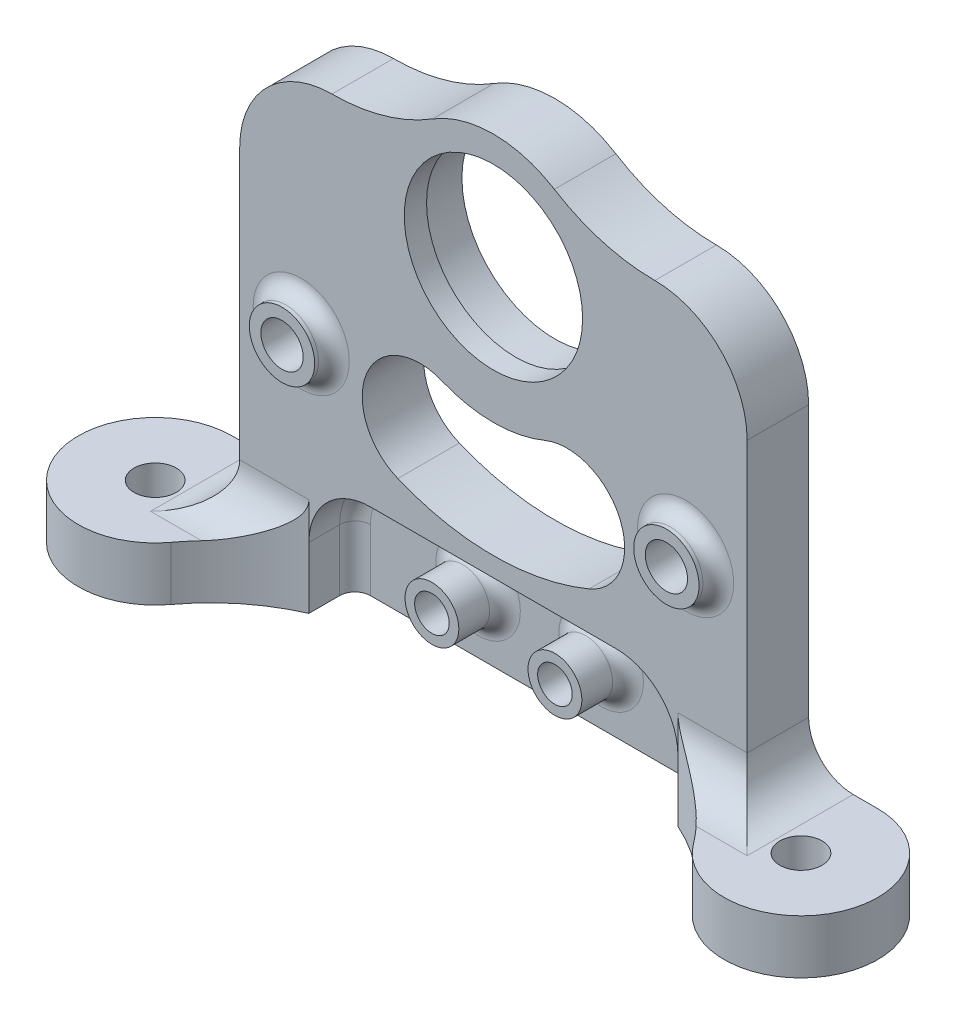
SolidWorks part; units mm, degrees
ref_plane "Front Plane" through (0, 0, 0) normal (0, 0, 1) x (1, 0, 0)
ref_plane "Top Plane" through (0, 0, 0) normal (0, 1, 0) x (1, 0, 0)
ref_plane "Right Plane" through (0, 0, 0) normal (1, 0, 0) x (0, 0, -1)
sketch "Sketch1" plane through (0, 0, 0) normal (0, 0, 1) x (1, 0, 0)
  line L1 (0, 15) -> (33, 15)
  line L2 (0, 15) -> (0, -51)
  line L3 (0, -51) -> (33, -51)
  line L4 (33, 15) -> (33, -51)
  point P5 (0, 0)
  dimension "D1" = 33
  dimension "D2" = 66
  dimension "D4" = 15
extrude "Boss-Extrude1" add sketch "Sketch1" along normal blind 8 separate body
sketch "Sketch3" plane through (0, 0, 8) normal (0, 0, 1) x (1, 0, 0)
  line L0 (0, 15) -> (0, -51) construction
  line L1 (33, 15) -> (0, 15) construction
  line L2 (9.5671, -23.097) -> (0, 0) construction
  line L3 (-17.5, 0) -> (-32.5, 0)
  line L4 (33, -51) -> (33, 15) construction
  line L5 (0, -51) -> (33, -51) construction
  circle A0 centre (25, -20) radius 2.75
  circle A1 centre (0, 0) radius 11.6
  arc A2 (-17.5, 0) -> (6.697, -16.1679) centre (0, 0) ccw
  arc A3 (-32.5, 0) -> (12.4372, -30.0261) centre (0, 0) ccw
  arc A4 (12.4372, -30.0261) -> (6.697, -16.1679) centre (9.5671, -23.097) ccw
  dimension "D1" = 5.5
  dimension "D2" = 23.2
  dimension "D4" = 35
  dimension "D5" = 65
  dimension "D3" = 15
  dimension "D6" = 22.5
  dimension "D7" = 8
  dimension "D8" = 31
extrude "Cut-Extrude1" cut sketch "Sketch3" against normal through all
sketch "Sketch4" plane through (0, 0, 8) normal (0, 0, 1) x (1, 0, 0)
  circle A0 centre (25, -20) radius 2.75 construction
  circle A1 centre (25, -20) radius 2.75
  circle A2 centre (25, -20) radius 4.25
  dimension "D1" = 8.5
extrude "Boss-Extrude3" add sketch "Sketch4" along normal blind 2.5
sketch "Sketch6" plane through (0, 0, 0) normal (0, 0, -1) x (-1, 0, 0)
  circle A0 centre (0, 0) radius 12.1
  dimension "D1" = 24.2
extrude "Cut-Extrude2" cut sketch "Sketch6" against normal blind 5.1
sketch "Sketch17" plane through (0, 0, 0) normal (0, 0, -1) x (-1, 0, 0)
  line L0 (-33, -51) -> (-33, 15) construction
  line L2 (0, 15) -> (0, 35)
  line L3 (0, 35) -> (-33, 35)
  line L4 (-33, 35) -> (-33, -3)
  line L5 (-21, -3) -> (-33, -3) construction
  line L6 (-33, 15) -> (0, 15) construction
  line L7 (-21, 9) -> (-21, -3) construction
  arc A0 (0, 15) -> (-7.9245, 12.7358) centre (0, 0) ccw
  arc A1 (-21, 9) -> (-7.9245, 12.7358) centre (-21, 33.75) ccw
  arc A3 (-21, 9) -> (-33, -3) centre (-21, -3) ccw
  dimension "D1" = 20
  dimension "D2" = 12
  dimension "D3" = 18
extrude "Cut-Extrude6" cut sketch "Sketch17" against normal through all
sketch "Sketch10" plane through (0, -51, 0) normal (0, -1, 0) x (1, 0, 0)
  line L0 (42, 0) -> (32, 0)
  line L1 (0, 0) -> (33, 0) construction
  line L2 (32, 10) -> (32, 0)
  line L3 (33, 8) -> (33, 0) construction
  arc A0 (42, 0) -> (32, 10) centre (42, 10) ccw
  circle A1 centre (42, 10) radius 2.75
  dimension "D1" = 5.5
  dimension "D2" = 20
  dimension "D3" = 1
extrude "Boss-Extrude4" add sketch "Sketch10" against normal blind 7
sketch "Sketch11" plane through (0, 0, 8) normal (0, 0, 1) x (1, 0, 0)
  line L1 (0, -51) -> (24, -51)
  line L2 (0, -51) -> (0, -35)
  line L3 (0, -35) -> (16, -35)
  line L4 (24, -51) -> (24, -43)
  arc A0 (16, -35) -> (24, -43) centre (16, -43) cw
  dimension "D1" = 8
  dimension "D2" = 16
  dimension "D3" = 24
extrude "Cut-Extrude3" cut sketch "Sketch11" against normal blind 6
sketch "Sketch12" plane through (0, 0, 2) normal (0, 0, 1) x (1, 0, 0)
  line L0 (8, -43) -> (0, -43) construction
  line L1 (0, -35) -> (0, -51) construction
  circle A0 centre (8, -43) radius 2.75
  dimension "D1" = 5.5
  dimension "D2" = 8
extrude "Cut-Extrude4" cut sketch "Sketch12" against normal blind 6
fillet "Fillet7" radius 2 3 edges at (24, -47, 2) (8, -35, 2) (21.6569, -37.3431, 2)
fillet "Fillet5" radius 25 1 edges at (32, -47.5, 8)
fillet "Fillet6" radius 5.8 2 edges at (33, -44, 4) (28.5, -44, 8)
sketch "Sketch15" plane through (0, 0, 0) normal (0, 0, 1) x (1, 0, 0)
  circle A0 centre (8, -43) radius 3.5
  circle A5 centre (8, -43) radius 2.25
  circle A6 centre (8, -43) radius 2.25
  dimension "D1" = 7
  dimension "D2" = 0.5
extrude "Boss-Extrude5" add sketch "Sketch15" along normal up to surface (8 mm away) up to face at (13.3876, -16.4099, 8)
sketch "Sketch13" plane through (0, 0, 0) normal (0, 0, -1) x (-1, 0, 0)
  line L1 (-22.5463, -15.75) -> (-27.4537, -15.75)
  line L2 (-27.4537, -15.75) -> (-29.9075, -20)
  line L3 (-29.9075, -20) -> (-27.4537, -24.25)
  line L4 (-27.4537, -24.25) -> (-22.5463, -24.25)
  line L5 (-22.5463, -24.25) -> (-20.0925, -20)
  line L6 (-20.0925, -20) -> (-22.5463, -15.75)
  circle A0 centre (-25, -20) radius 4.25 construction
  dimension "D1" = 8.5
extrude "Cut-Extrude5" cut sketch "Sketch13" against normal blind 5
fillet "Fillet8" radius 2 2 edges at (4.5, -43, 2) (29.25, -20, 8)
mirror "Mirror1" about plane through (0, 15, 8) normal (1, 0, 0) of bodies 112 105
ref_plane "Mid Plane" through (0, 0, 0) normal (1, 0, 0) x (0, 0, -1)
